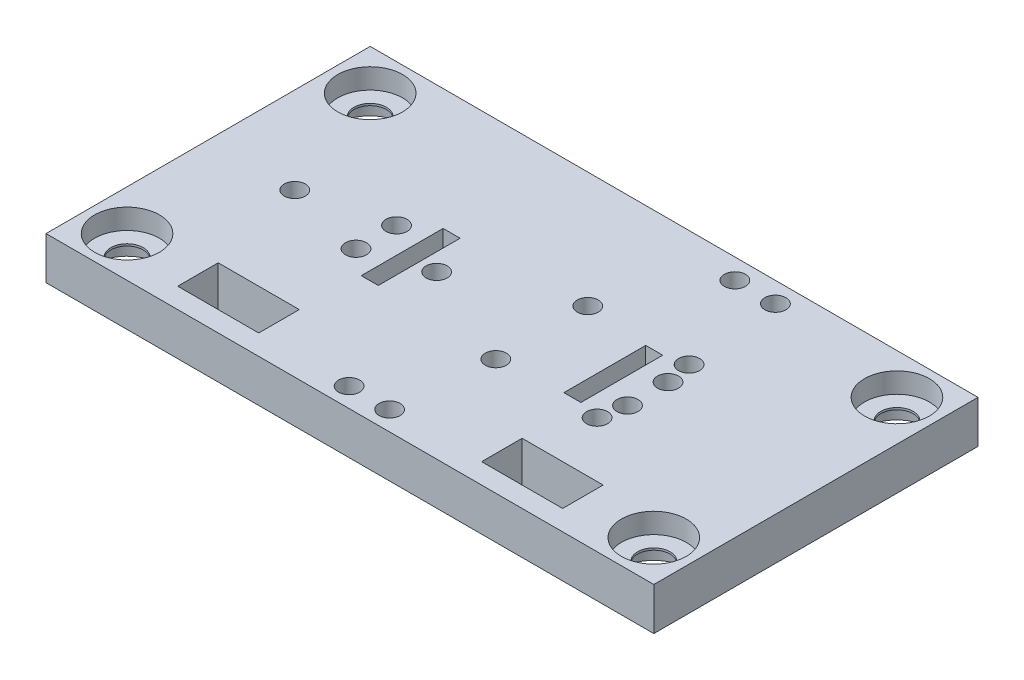
SolidWorks part; units mm, degrees
ref_plane "Front Plane" through (0, 0, 0) normal (0, 0, 1) x (1, 0, 0)
ref_plane "Top Plane" through (0, 0, 0) normal (0, 1, 0) x (1, 0, 0)
ref_plane "Right Plane" through (0, 0, 0) normal (1, 0, 0) x (0, 0, -1)
sketch "Sketch1" plane through (0, 0, 0) normal (0, 1, 0) x (1, 0, 0)
  line L1 (0, 0) -> (150, 0)
  line L2 (0, 0) -> (0, 80)
  line L3 (0, 80) -> (150, 80)
  line L4 (150, 0) -> (150, 80)
  dimension "D1" = 80
  dimension "D2" = 150
extrude "Boss-Extrude1" add sketch "Sketch1" along normal blind 10.5
sketch "Sketch10" plane through (0, 10.5, 0) normal (0, 1, 0) x (1, 0, 0)
  line L0 (75, 80) -> (75, 0) construction
  line L1 (0, 40) -> (150, 40) construction
  line L4 (0, 80) -> (0, 0)
  line L5 (0, 80) -> (0, 0) construction
  line L6 (0, 0) -> (150, 0)
  line L7 (0, 0) -> (150, 0) construction
  line L8 (150, 0) -> (150, 80)
  line L9 (150, 0) -> (150, 80) construction
  line L10 (150, 80) -> (0, 80)
  line L11 (150, 80) -> (0, 80) construction
  circle A0 centre (10, 10) radius 8
  circle A1 centre (140, 10) radius 8
  circle A3 centre (10, 70) radius 8
  circle A4 centre (140, 70) radius 8
  circle A5 centre (10, 10) radius 9
  circle A6 centre (10, 70) radius 9
  circle A7 centre (140, 70) radius 9
  circle A8 centre (140, 10) radius 9
  dimension "D4" = 16
  dimension "D2" = 10
  dimension "D3" = 10
  dimension "D1" = 0
  dimension "D5" = 1
extrude "Cut-Extrude8" cut sketch "Sketch10" against normal blind 5 contours A0 | A3 | A4 | A1 region at (10, 10.5, -10) region at (140, 10.5, -10) region at (10, 10.5, -70) region at (140, 10.5, -70)
ref_plane "MirrorPlane1" through (0, 5.25, 0) normal (0, 1, 0) x (1, 0, 0)
ref_plane "MirrorPlane2" through (0, 0, -40) normal (0, 0, 1) x (1, 0, 0)
ref_plane "MirrorPlane3" through (75, 0, 0) normal (-1, 0, 0) x (0, 0, 1)
mirror "Mirror1" about plane through (0, 5.25, 0) normal (0, 1, 0) of "Cut-Extrude8"
sketch "Sketch3" plane through (0, 10.5, 0) normal (0, 1, 0) x (1, 0, 0)
  line L0 (75, 80) -> (75, 0) construction
  line L5 (150, 80) -> (0, 80) construction
  line L6 (75, 5.775) -> (75, -5.775) construction
  line L7 (0, 0) -> (150, 0) construction
  line L8 (27.5, 15) -> (47.5, 15)
  line L9 (27.5, 15) -> (27.5, 5)
  line L10 (27.5, 5) -> (47.5, 5)
  line L11 (47.5, 15) -> (47.5, 5)
  line L12 (27.5, 15) -> (47.5, 5) construction
  line L13 (27.5, 5) -> (47.5, 15) construction
  line L15 (75, 80) -> (0, 0) construction
  line L16 (122.5, 5) -> (102.5, 5)
  line L17 (102.5, 15) -> (102.5, 5)
  line L18 (122.5, 15) -> (102.5, 15)
  line L19 (122.5, 15) -> (122.5, 5)
  point P0 (37.5, 10)
  point P16 (37.5, 40)
  dimension "D1" = 10
  dimension "D2" = 10
  dimension "D3" = 20
extrude "WireHoles" cut sketch "Sketch3" against normal up to next
sketch "Sketch6" plane through (0, 10.5, 0) normal (0, 1, 0) x (1, 0, 0)
  line L0 (75, 80) -> (75, 0) construction
  line L1 (150, 80) -> (0, 80) construction
  line L2 (0, 0) -> (150, 0) construction
  line L3 (38.9, 40) -> (21.4, 40) construction
  line L4 (73, 28.4) -> (4.8, 28.4) construction
  line L5 (73, 28.4) -> (73, 51.6) construction
  line L6 (73, 51.6) -> (4.8, 51.6) construction
  line L7 (4.8, 28.4) -> (4.8, 51.6) construction
  line L8 (73, 28.4) -> (4.8, 51.6) construction
  line L9 (73, 51.6) -> (4.8, 28.4) construction
  line L10 (38.9, 51.6) -> (38.9, 28.4) construction
  circle A0 centre (21.4, 40) radius 2.6
  circle A1 centre (56.4, 40) radius 2.6
  point P8 (38.9, 40)
  point P18 (75, 40)
  dimension "D5" = 5.2
  dimension "D1" = 68.2
  dimension "D2" = 23.2
  dimension "D3" = 2
  dimension "D4" = 17.5
extrude "4AACut" cut sketch "Sketch6" against normal blind 5.2
sketch "Sketch7" plane through (0, 10.5, 0) normal (0, 1, 0) x (1, 0, 0)
  line L0 (94.85, 51.35) -> (82.35, 51.35) construction
  line L1 (77, 42) -> (112.7, 42) construction
  line L2 (77, 42) -> (77, 60.7) construction
  line L3 (77, 60.7) -> (112.7, 60.7) construction
  line L4 (112.7, 42) -> (112.7, 60.7) construction
  line L5 (77, 42) -> (112.7, 60.7) construction
  line L6 (77, 60.7) -> (112.7, 42) construction
  line L7 (94.85, 60.7) -> (94.85, 42) construction
  line L8 (75, 80) -> (75, 0) construction
  line L9 (150, 80) -> (0, 80) construction
  line L10 (0, 0) -> (150, 0) construction
  line L11 (0, 40) -> (150, 40) construction
  line L12 (0, 80) -> (0, 0) construction
  line L13 (150, 0) -> (150, 80) construction
  circle A0 centre (82.35, 51.35) radius 2.6
  circle A1 centre (56.4, 40) radius 2.6 construction
  circle A2 centre (107.35, 51.35) radius 2.6
  circle A3 centre (82.35, 28.65) radius 2.6
  circle A4 centre (107.35, 28.65) radius 2.6
  point P0 (94.85, 51.35)
  dimension "D1" = 35.7
  dimension "D2" = 18.7
  dimension "D3" = 2
  dimension "D4" = 2
  dimension "D5" = 12.5
extrude "2AACut" cut sketch "Sketch7" against normal blind 5.2
sketch "Sketch5" plane through (0, 10.5, 0) normal (0, 1, 0) x (1, 0, 0)
  line L0 (75, 80) -> (75, 0) construction
  line L5 (150, 80) -> (0, 80) construction
  line L6 (0, 0) -> (150, 0) construction
  line L7 (50, 40) -> (75, 40) construction
  line L12 (47.9, 29.9) -> (52.1, 29.9)
  line L13 (47.9, 29.9) -> (47.9, 50.1)
  line L14 (47.9, 50.1) -> (52.1, 50.1)
  line L15 (52.1, 29.9) -> (52.1, 50.1)
  line L16 (47.9, 29.9) -> (52.1, 50.1) construction
  line L17 (47.9, 50.1) -> (52.1, 29.9) construction
  line L18 (102.1, 50.1) -> (97.9, 50.1)
  line L19 (97.9, 29.9) -> (97.9, 50.1)
  line L20 (102.1, 29.9) -> (97.9, 29.9)
  line L21 (102.1, 29.9) -> (102.1, 50.1)
  point P0 (50, 40)
  dimension "D1" = 25
  dimension "D2" = 4.2
  dimension "D3" = 20.2
extrude "ArduinoMegaCut" cut sketch "Sketch5" against normal blind 5.2
sketch "Sketch8" plane through (0, 10.5, 0) normal (0, 1, 0) x (1, 0, 0)
  line L0 (150, 80) -> (0, 80) construction
  line L5 (62.4, -2.5) -> (87.6, -2.5) construction
  line L6 (62.4, -2.5) -> (62.4, 12.1) construction
  line L7 (62.4, 12.1) -> (87.6, 12.1) construction
  line L8 (87.6, -2.5) -> (87.6, 12.1) construction
  line L9 (75, 80) -> (75, 0) construction
  line L10 (0, 0) -> (150, 0) construction
  line L11 (87.6, 4.8) -> (62.4, 4.8) construction
  circle A1 centre (70, 4.8) radius 2.6
  circle A2 centre (56.4, 40) radius 2.6 construction
  circle A3 centre (80, 4.8) radius 2.6
  point P10 (75, 12.1)
  dimension "D1" = 14.6
  dimension "D2" = 25.2
  dimension "D3" = 2.5
  dimension "D4" = 5
extrude "MPUCut" cut sketch "Sketch8" against normal blind 5.2
sketch "Sketch9" plane through (0, 10.5, 0) normal (0, 1, 0) x (1, 0, 0)
  line L0 (150, 0) -> (150, 80) construction
  line L1 (97, 51.225) -> (120, 51.225)
  line L2 (97, 51.225) -> (97, 28.775)
  line L3 (97, 28.775) -> (120, 28.775)
  line L4 (120, 51.225) -> (120, 28.775)
  line L5 (97, 51.225) -> (120, 28.775) construction
  line L6 (97, 28.775) -> (120, 51.225) construction
  line L9 (0, 40) -> (150, 40) construction
  line L10 (0, 80) -> (0, 0) construction
  line L11 (75, 80) -> (75, 0) construction
  line L12 (150, 80) -> (0, 80) construction
  line L13 (0, 0) -> (150, 0) construction
  circle A0 centre (108.5, 45) radius 2.6
  circle A1 centre (107.35, 51.35) radius 2.6 construction
  circle A2 centre (108.5, 35) radius 2.6
  circle A3 centre (41.5, 35) radius 2.6
  circle A4 centre (41.5, 45) radius 2.6
  point P0 (108.5, 40)
  dimension "D1" = 22.45
  dimension "D2" = 23
  dimension "D3" = 5
  dimension "D4" = 30
extrude "Cut-Extrude7" cut sketch "Sketch9" against normal up to next contours A0 | A2 | A4 | A3 region at (108.5, 10.5, -45) region at (108.5, 10.5, -35) region at (41.5, 10.5, -45)
sketch "Sketch11" plane through (0, 5.5, 0) normal (0, 1, 0) x (1, 0, 0)
  line L0 (0, 40) -> (150, 40) construction
  line L1 (0, 80) -> (0, 0) construction
  line L2 (150, 0) -> (150, 80) construction
  line L3 (75, 80) -> (75, 0) construction
  line L4 (150, 80) -> (0, 80) construction
  line L5 (0, 0) -> (150, 0) construction
  circle A0 centre (10, 10) radius 4
  circle A1 centre (10, 70) radius 4
  circle A2 centre (140, 70) radius 4
  circle A3 centre (140, 10) radius 4
  dimension "D1" = 8
extrude "Cut-Extrude9" cut sketch "Sketch11" against normal up to surface (0.5 mm away) up to face at (10, 5, -62)
sketch "Sketch12" plane through (0, 10.5, 0) normal (0, 1, 0) x (1, 0, 0)
  line L0 (100, 80) -> (100, 0) construction
  line L1 (150, 80) -> (0, 80) construction
  line L2 (0, 0) -> (150, 0) construction
  line L3 (150, 0) -> (150, 80) construction
  circle A0 centre (95, 75) radius 2.6
  circle A1 centre (82.35, 51.35) radius 2.6 construction
  circle A4 centre (105, 75) radius 2.6
  dimension "D1" = 50
  dimension "D2" = 10
  dimension "D3" = 5
extrude "Cut-Extrude10" cut sketch "Sketch12" against normal blind 5
equation "\"Depth\"= 5.20"
